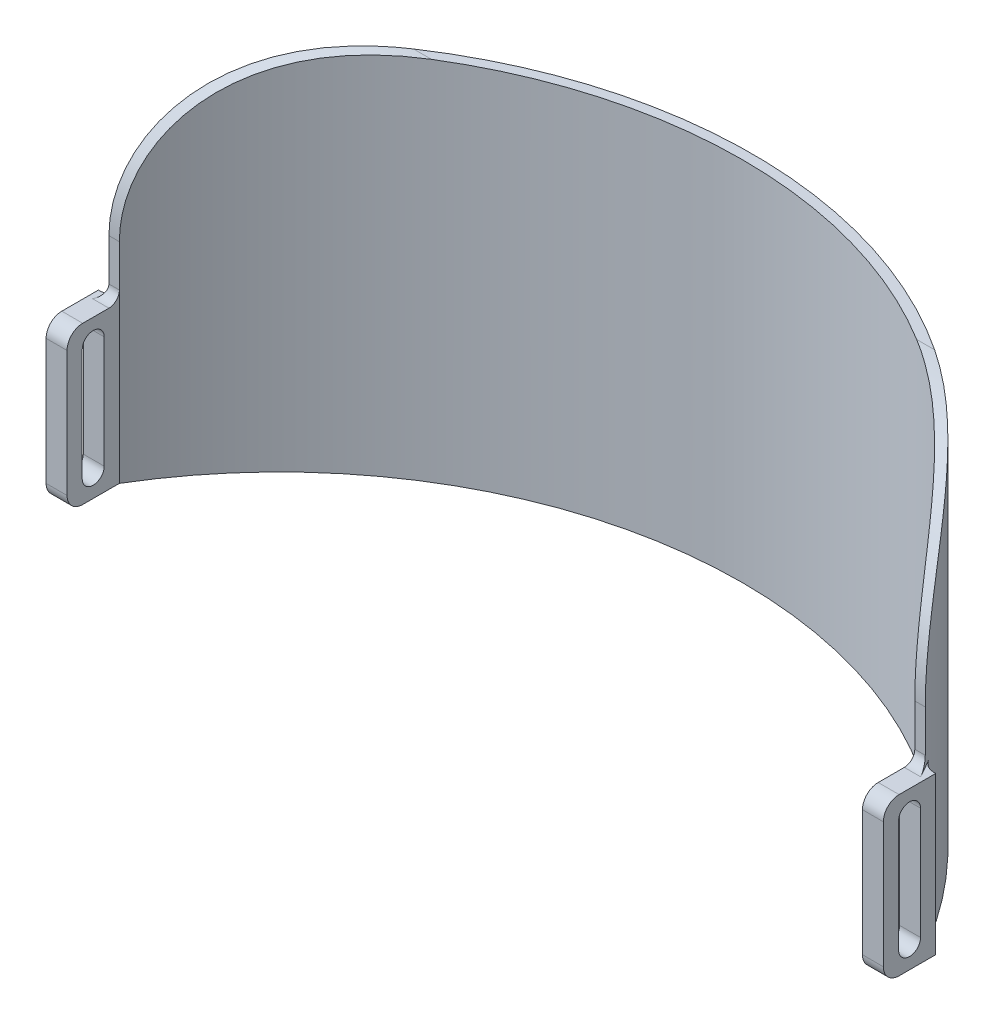
SolidWorks part; units mm, degrees
ref_plane "Front" through (0, 0, 0) normal (0, 0, 1) x (1, 0, 0)
ref_plane "Top" through (0, 0, 0) normal (0, 1, 0) x (1, 0, 0)
ref_plane "Right" through (0, 0, 0) normal (1, 0, 0) x (0, 0, -1)
sketch "Sketch1" plane through (0, 0, 0) normal (0, 1, 0) x (1, 0, 0)
  line L4 (-78, 0) -> (-76, 0)
  line L5 (78, 0) -> (76, 0)
  arc A4 (-78, 0) -> (78, 0) centre (0, -45.0825) cw
  arc A6 (-76, 0) -> (76, 0) centre (0, -45.4421) cw
  point P4 (0, 0)
  point P9 (0, 0)
  point P12 (0, 0)
extrude "Boss-Extrude1" add sketch "Sketch1" along normal blind 70
sketch "Sketch3" plane through (0, 0, 0) normal (0, 0, 1) x (1, 0, 0)
  line L1 (-76, 0) -> (-80, 0)
  line L2 (-76, 0) -> (-76, 30)
  line L3 (-76, 30) -> (-80, 30)
  line L4 (-80, 0) -> (-80, 30)
  line L5 (76, 0) -> (80, 0)
  line L6 (76, 0) -> (76, 30)
  line L7 (76, 30) -> (80, 30)
  line L8 (80, 0) -> (80, 30)
  dimension "D1" = 4
  dimension "D2" = 4
extrude "Boss-Extrude2" add sketch "Sketch3" along normal blind 10
sketch "Sketch4" plane through (-80, 0, 0) normal (-1, 0, 0) x (0, 0, 1)
  line L1 (5, 25.7) -> (5, 4.3) construction
  line L3 (7.1, 25.7) -> (7.1, 4.3)
  line L8 (2.9, 25.7) -> (2.9, 4.3)
  arc A0 (7.1, 25.7) -> (2.9, 25.7) centre (5, 25.7) ccw
  arc A1 (2.9, 4.3) -> (7.1, 4.3) centre (5, 4.3) ccw
  point P8 (5, 15)
extrude "Cut-Extrude1" cut sketch "Sketch4" against normal blind 168
fillet "Fillet2" radius 3 6 edges at (78, 0, 10) (78, 30, 10) (-78, 0, 10) (-78, 30, 10) (78, 15, 0) (-78, 15, 0)
fillet "Fillet3" radius 2 2 edges at (77, 30, 0) (-77, 30, 0)
fillet "Fillet4" radius 30 2 edges at (77, 70, 0) (-77, 70, 0)
